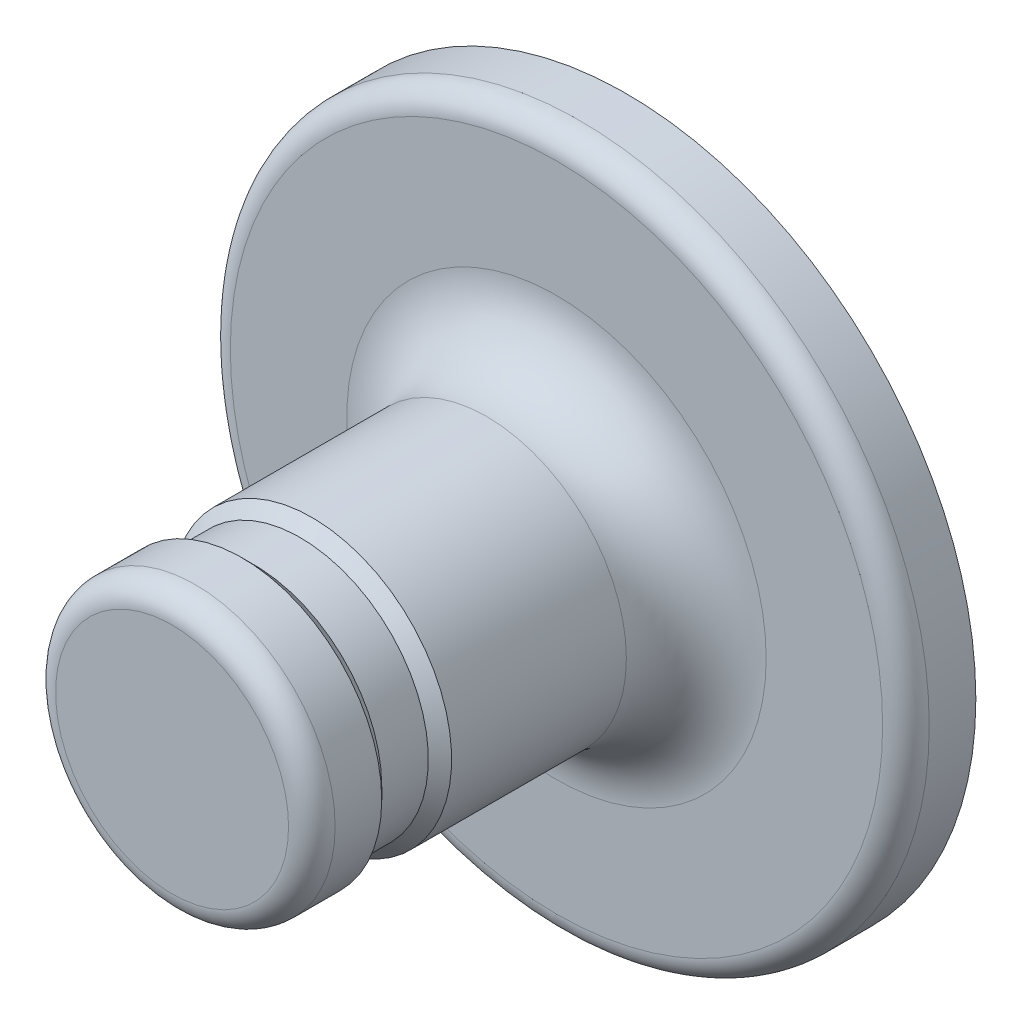
SolidWorks part; units mm, degrees
ref_plane "前视基准面" through (0, 0, 0) normal (0, 0, 1) x (1, 0, 0)
ref_plane "上视基准面" through (0, 0, 0) normal (0, 1, 0) x (1, 0, 0)
ref_plane "右视基准面" through (0, 0, 0) normal (1, 0, 0) x (0, 0, -1)
other "Configuration Table"
sketch "草图1" plane through (0, 0, 0) normal (0, 0, 1) x (1, 0, 0)
  circle A0 centre (0, 0) radius 15
  dimension "D1" = 30
extrude "凸台-拉伸1" add sketch "草图1" along normal blind 3
sketch "草图2" plane through (0, 0, 3) normal (0, 0, 1) x (1, 0, 0)
  circle A0 centre (0, 0) radius 6
  dimension "D1" = 12
extrude "凸台-拉伸2" add sketch "草图2" along normal blind 16.5
fillet "圆角1" radius 3 1 edges at (6, 0, 3)
fillet "圆角2" radius 1 1 edges at (15, 0, 3)
fillet "圆角3" radius 1 1 edges at (6, 0, 19.5)
ref_plane "基准面1" through (0, 0, 13) normal (0, 0, -1) x (-1, 0, 0)
sketch "草图3" plane through (0, 0, 13) normal (0, 0, -1) x (-1, 0, 0)
  circle A0 centre (0, 0) radius 5.5
  circle A1 centre (0, 0) radius 6
  dimension "D1" = 12
  dimension "D2" = 11
extrude "切除-拉伸1" cut sketch "草图3" against normal blind 4
chamfer "倒角1" distance 1 angle 45 2 edges at (-5.5, 0, 13) (-5.5, 0, 17)
